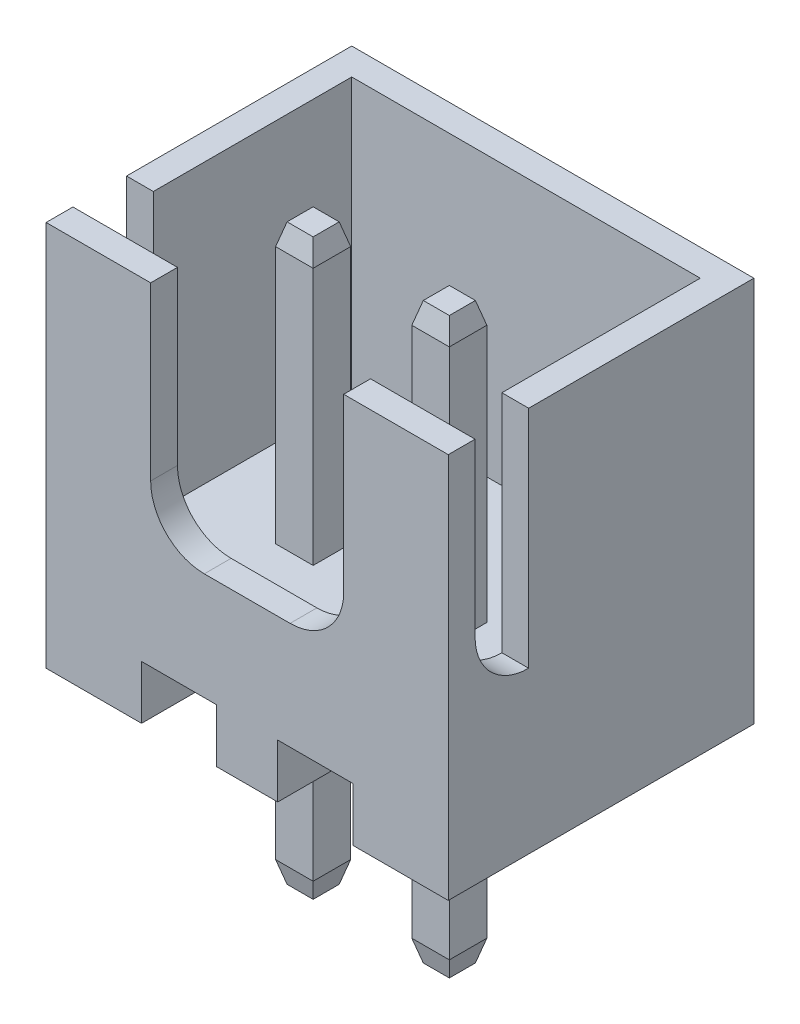
SolidWorks part; units mm, degrees
ref_plane "Alzado" through (0, 0, 0) normal (0, 0, 1) x (1, 0, 0)
ref_plane "Planta" through (0, 0, 0) normal (0, 1, 0) x (1, 0, 0)
ref_plane "Vista lateral" through (0, 0, 0) normal (1, 0, 0) x (0, 0, -1)
sketch "Croquis2" plane through (0, 0, 0) normal (0, 1, 0) x (1, 0, 0)
  line L1 (-3.75, 2.85) -> (3.75, 2.85)
  line L2 (-3.75, 2.85) -> (-3.75, -2.85)
  line L3 (-3.75, -2.85) -> (3.75, -2.85)
  line L4 (3.75, 2.85) -> (3.75, -2.85)
  line L5 (-3.75, 2.85) -> (3.75, -2.85) construction
  line L6 (-3.75, -2.85) -> (3.75, 2.85) construction
  point P0 (0, 0)
  dimension "D1" = 7.5
  dimension "D2" = 5.7
extrude "Saliente-Extruir1" add sketch "Croquis2" along normal blind 7.2
sketch "Croquis3" plane through (0, 7.2, 0) normal (0, 1, 0) x (1, 0, 0)
  line L0 (3.75, 2.85) -> (-3.75, 2.85) construction
  line L1 (-3.25, -2.35) -> (3.25, -2.35)
  line L2 (-3.25, -2.35) -> (-3.25, 2.35)
  line L3 (-3.25, 2.35) -> (3.25, 2.35)
  line L4 (3.25, -2.35) -> (3.25, 2.35)
  line L5 (-3.25, -2.35) -> (3.25, 2.35) construction
  line L6 (-3.25, 2.35) -> (3.25, -2.35) construction
  line L7 (-3.75, 2.85) -> (-3.75, -2.85) construction
  point P0 (0, 0)
  dimension "D1" = 0.5
  dimension "D2" = 0.5
extrude "Cortar-Extruir1" cut sketch "Croquis3" against normal offset from surface (5.2 mm away) 2 up to face at (0, 0, 0)
sketch "Croquis4" plane through (0, 7.2, 0) normal (0, 1, 0) x (1, 0, 0)
  line L0 (-3.25, -2.35) -> (3.25, -2.35) construction
  line L1 (-1.8, -2.85) -> (1.8, -2.85)
  line L2 (-1.8, -2.85) -> (-1.8, -2.35)
  line L3 (-1.8, -2.35) -> (1.8, -2.35)
  line L4 (1.8, -2.85) -> (1.8, -2.35)
  line L5 (-1.8, -2.85) -> (1.8, -2.35) construction
  line L6 (-1.8, -2.35) -> (1.8, -2.85) construction
  line L7 (-3.75, -2.85) -> (3.75, -2.85) construction
  point P0 (0, -2.6)
  dimension "D1" = 3.6
extrude "Cortar-Extruir2" cut sketch "Croquis4" against normal offset from surface (4.2 mm away) 3 up to face at (0, 0, 0)
sketch "Croquis5" plane through (3.75, 0, 0) normal (1, 0, 0) x (0, 0, -1)
  line L0 (-2.85, 7.2) -> (2.85, 7.2) construction
  line L1 (-2.35, 7.2) -> (-1.35, 7.2)
  line L2 (-2.35, 7.2) -> (-2.35, 3)
  line L3 (-2.35, 3) -> (-1.35, 3)
  line L4 (-1.35, 7.2) -> (-1.35, 3)
  line L5 (-2.85, 0) -> (2.85, 0) construction
  line L8 (-2.35, 3) -> (-2.35, 7.2) construction
  dimension "D2" = 1
  dimension "D3" = 3
extrude "Cortar-Extruir3" cut sketch "Croquis5" against normal through all
fillet "Redondeo1" radius 1 4 edges at (1.8, 3, 2.6) (-1.8, 3, 2.6) (-3.5, 3, 2.35) (3.5, 3, 2.35)
sketch "Croquis6" plane through (0, 0, 0) normal (0, -1, 0) x (1, 0, 0)
  line L0 (-3.75, 2.85) -> (3.75, 2.85) construction
  line L1 (-1.62, 0.7) -> (-0.92, 0.7)
  line L2 (-1.62, 0.7) -> (-1.62, 0)
  line L3 (-1.62, 0) -> (-0.92, 0)
  line L4 (-0.92, 0.7) -> (-0.92, 0)
  line L5 (-1.62, 0.7) -> (-0.92, 0) construction
  line L6 (-1.62, 0) -> (-0.92, 0.7) construction
  line L8 (0.92, 0.7) -> (1.62, 0.7)
  line L9 (0.92, 0.7) -> (0.92, 0)
  line L10 (0.92, 0) -> (1.62, 0)
  line L11 (1.62, 0.7) -> (1.62, 0)
  line L12 (0.92, 0.7) -> (1.62, 0) construction
  line L13 (0.92, 0) -> (1.62, 0.7) construction
  point P0 (-1.27, 0.35)
  point P8 (1.27, 0.35)
  dimension "D1" = 0.7
  dimension "D2" = 0.7
  dimension "D3" = 2.5
  dimension "D4" = 1.27
  dimension "D5" = 1.27
sketch "Croquis7" plane through (0, 0, 0) normal (0, -1, 0) x (1, 0, 0)
  line L0 (-3.75, 2.85) -> (3.75, 2.85) construction
  line L1 (-1.97, 2.85) -> (-0.57, 2.85)
  line L2 (-1.97, 2.85) -> (-1.97, -2.85)
  line L3 (-1.97, -2.85) -> (-0.57, -2.85)
  line L4 (-0.57, 2.85) -> (-0.57, -2.85)
  line L5 (-1.97, 2.85) -> (-0.57, -2.85) construction
  line L6 (-1.97, -2.85) -> (-0.57, 2.85) construction
  line L7 (3.75, -2.85) -> (-3.75, -2.85) construction
  line L9 (0.57, 2.85) -> (1.97, 2.85)
  line L10 (0.57, 2.85) -> (0.57, -2.85)
  line L11 (0.57, -2.85) -> (1.97, -2.85)
  line L12 (1.97, 2.85) -> (1.97, -2.85)
  line L13 (0.57, 2.85) -> (1.97, -2.85) construction
  line L14 (0.57, -2.85) -> (1.97, 2.85) construction
  point P0 (-1.27, 0)
  point P11 (1.27, 0)
  dimension "D1" = 1.4
  dimension "D2" = 1.4
extrude "Cortar-Extruir4" cut sketch "Croquis7" against normal blind 1
extrude "Saliente-Extruir2" add sketch "Croquis6" along normal blind 3.5 and the other way up to surface (7.2 mm away) other way up to face at (0, 7.2, -0.625)
chamfer "Chaflán1" distance 0.4 angle 15 8 edges at (-1.27, -3.5, 0) (-1.62, -3.5, 0.35) (-1.27, -3.5, 0.7) (-0.92, -3.5, 0.35) (1.27, -3.5, 0) (0.92, -3.5, 0.35) (1.27, -3.5, 0.7) (1.62, -3.5, 0.35) first distance on face at (-1.27, -1.25, 0) first distance on face at (-1.62, -1.25, 0.35) first distance on face at (-1.27, -1.25, 0.7) first distance on face at (-0.92, -1.25, 0.35) first distance on face at (1.27, -1.25, 0) first distance on face at (0.92, -1.25, 0.35) first distance on face at (1.27, -1.25, 0.7) first distance on face at (1.62, -1.25, 0.35)
chamfer "Chaflán2" distance 0.4 angle 15 4 edges at (-1.62, 7.2, 0.35) (-1.27, 7.2, 0.7) (-1.27, 7.2, 0) (-0.92, 7.2, 0.35) first distance on face at (-1.62, 4.6, 0.35) first distance on face at (-1.27, 4.6, 0.7) first distance on face at (-1.27, 4.6, 0) first distance on face at (-0.92, 4.6, 0.35)
chamfer "Chaflán3" distance 0.4 angle 15 4 edges at (0.92, 7.2, 0.35) (1.27, 7.2, 0.7) (1.27, 7.2, 0) (1.62, 7.2, 0.35) first distance on face at (0.92, 4.6, 0.35) first distance on face at (1.27, 4.6, 0.7) first distance on face at (1.27, 4.6, 0) first distance on face at (1.62, 4.6, 0.35)
